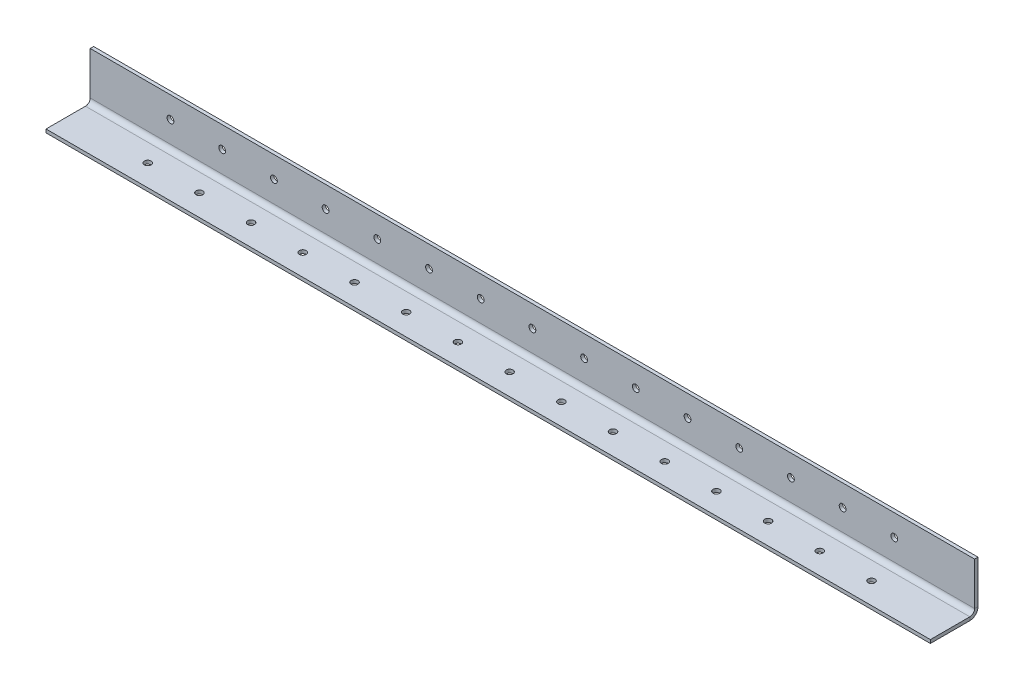
SolidWorks part; units mm, degrees
note: The reader was unsure of these and kept them because the rebuilt part matched: flange length of "Edge-Flange1".
material "Plain Carbon Steel"
ref_plane "Front Plane" through (0, 0, 0) normal (0, 0, 1) x (1, 0, 0)
ref_plane "Top Plane" through (0, 0, 0) normal (0, 1, 0) x (1, 0, 0)
ref_plane "Right Plane" through (0, 0, 0) normal (1, 0, 0) x (0, 0, -1)
sketch "Sketch1" plane through (0, 0, 0) normal (0, 0, 1) x (1, 0, 0)
  line L1 (-1300, -75) -> (1300, -75)
  line L2 (-1300, -75) -> (-1300, 75)
  line L3 (-1300, 75) -> (1300, 75)
  line L4 (1300, -75) -> (1300, 75)
  line L5 (-1300, -75) -> (1300, 75) construction
  line L6 (-1300, 75) -> (1300, -75) construction
  point P0 (0, 0)
  dimension "D1" = 2600
  dimension "D2" = 150
base flange "Base-Flange1" sketch "Sketch1" thickness 10 reverse thickness direction no parameters "D1"=3
edge flange "Edge-Flange1" sketch "Sketch10" flange angle 90 flange length 140 flange position material inside bend radius 14 thickness 10 relief rectangular parameters "D6"=10, "D8"=1
sketch "Sketch10" plane through (0, -75, 0) normal (0, -1, 0) x (1, 0, 0)
  line L0 (-1300, 0) -> (1300, 0) construction
  line L1 (-1300, 0) -> (1300, 0)
  line L2 (-1300, 0) -> (-1300, 130)
  line L3 (-1300, 130) -> (1300, 130)
  line L4 (1300, 130) -> (1300, 0)
bend "EdgeBend1" bend radius 14 bend angle 90 parameters "D5"=1
sketch "Sketch12" plane through (0, -75, 0) normal (0, -1, 0) x (-1, 0, 0)
  line L0 (1300, 0) -> (1300, -130) construction
  line L2 (-1300, -130) -> (1300, -130) construction
  circle A0 centre (1064, -67) radius 10
  dimension "D1" = 20
  dimension "D2" = 236
  dimension "D3" = 63
extrude "Cut-Extrude1" cut sketch "Sketch12" against normal blind 10
sketch "Sketch13" plane through (0, 0, -10) normal (0, 0, -1) x (-1, 0, 0)
  line L3 (1300, 75) -> (1300, -51) construction
  circle A0 centre (1064, 12) radius 10
  point P6 (1300, 12)
  dimension "D1" = 20
  dimension "D2" = 236
extrude "Cut-Extrude2" cut sketch "Sketch13" against normal blind 10
pattern_linear "LPattern1" count 15 spacing 152 along (1, 0, 0) of "Cut-Extrude1", "Cut-Extrude2"
sketch "Bend-Lines1" [suppressed] plane through (0, 0, 0) normal (0, 1, 0) x (1, 0, 0)
sketch "Bounding-Box1" [suppressed] plane through (0, 0, 0) normal (0, 1, 0) x (1, 0, 0)
sheet metal parameters "Sheet-Metal1" thickness 10 parameters "D1"=3
flat pattern "Flat-Pattern1" [suppressed]
sketch "Bend-Lines2" plane through (0, 0, 0) normal (0, 1, 0) x (1, 0, 0)
sketch3d "Bounding-Box2" [suppressed]
  line L0 (800, -100, 0) -> (-800, -100, 0) construction
  line L1 (800, 100, 0) -> (-800, 100, 0) construction
  line L2 (800, -100, 0) -> (800, 100, 0) construction
  line L3 (-800, -100, 0) -> (-800, 100, 0) construction
sheet metal parameters "Sheet-Metal2" thickness 10 parameters "D1"=3
flat pattern "Flat-Pattern1"
sketch "Bend-Lines2" plane through (0, 0, 0) normal (0, 0, 1) x (1, 0, 0)
  line L1 (-950, -65.9226) -> (950, -65.9226) construction
  line L3 (-950, -65.9226) -> (950, -65.9226) construction
sketch3d "Bounding-Box2" [suppressed]
  line L0 (-950, -206.8451, 0) -> (950, -206.8451, 0) construction
  line L1 (-950, 75, 0) -> (950, 75, 0) construction
  line L2 (-950, -206.8451, 0) -> (-950, 75, 0) construction
  line L3 (950, -206.8451, 0) -> (950, 75, 0) construction
bend of the flat pattern "Flatten-<EdgeBend1>1"
sheet metal parameters "Sheet-Metal3" thickness 10 parameters "D1"=3
flat pattern "Flat-Pattern1"
sketch "Bend-Lines2" plane through (0, 0, 0) normal (0, 0, 1) x (1, 0, 0)
  line L1 (-950, -65.9226) -> (950, -65.9226) construction
  line L3 (-950, -65.9226) -> (950, -65.9226) construction
sketch3d "Bounding-Box2" [suppressed]
  line L0 (-950, -206.8451, 0) -> (950, -206.8451, 0) construction
  line L1 (-950, 75, 0) -> (950, 75, 0) construction
  line L2 (-950, -206.8451, 0) -> (-950, 75, 0) construction
  line L3 (950, -206.8451, 0) -> (950, 75, 0) construction
bend of the flat pattern "Flatten-<EdgeBend1>1"
sheet metal parameters "Sheet-Metal4" thickness 10 parameters "D1"=3
flat pattern "Flat-Pattern1"
sketch "Bend-Lines2" plane through (0, 0, 0) normal (0, 0, 1) x (1, 0, 0)
  line L1 (-1300, -65.9226) -> (1300, -65.9226) construction
  line L3 (-1300, -65.9226) -> (1300, -65.9226) construction
sketch3d "Bounding-Box2" [suppressed]
  line L0 (-1300, -196.8451, 0) -> (1300, -196.8451, 0) construction
  line L1 (-1300, 75, 0) -> (1300, 75, 0) construction
  line L2 (-1300, -196.8451, 0) -> (-1300, 75, 0) construction
  line L3 (1300, -196.8451, 0) -> (1300, 75, 0) construction
bend of the flat pattern "Flatten-<EdgeBend1>1"
sheet metal parameters "Sheet-Metal5" thickness 10 parameters "D1"=3
flat pattern "Flat-Pattern1"
sketch "Bend-Lines2" plane through (0, 0, 0) normal (0, 0, 1) x (1, 0, 0)
  line L1 (-950, -65.9226) -> (950, -65.9226) construction
  line L3 (-950, -65.9226) -> (950, -65.9226) construction
sketch3d "Bounding-Box2" [suppressed]
  line L0 (-950, -206.8451, 0) -> (950, -206.8451, 0) construction
  line L1 (-950, 75, 0) -> (950, 75, 0) construction
  line L2 (-950, -206.8451, 0) -> (-950, 75, 0) construction
  line L3 (950, -206.8451, 0) -> (950, 75, 0) construction
bend of the flat pattern "Flatten-<EdgeBend1>1"
